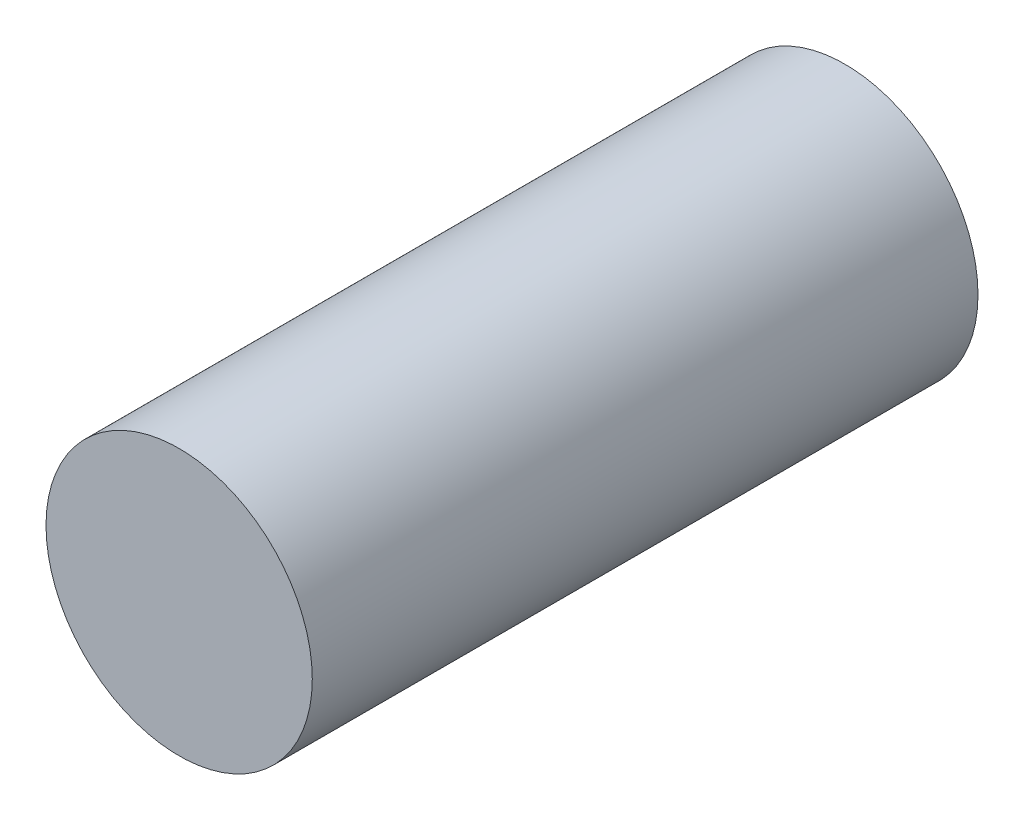
SolidWorks part; units mm, degrees
ref_plane "Front Plane" through (0, 0, 0) normal (0, 0, 1) x (1, 0, 0)
ref_plane "Top Plane" through (0, 0, 0) normal (0, 1, 0) x (1, 0, 0)
ref_plane "Right Plane" through (0, 0, 0) normal (1, 0, 0) x (0, 0, -1)
sketch "Sketch6" plane through (0, 0, 0) normal (0, 0, 1) x (1, 0, 0)
  circle A0 centre (0, 0) radius 6.35
  dimension "D1" = 12.7
extrude "Extrude2" add sketch "Sketch6" along normal blind 31.75
